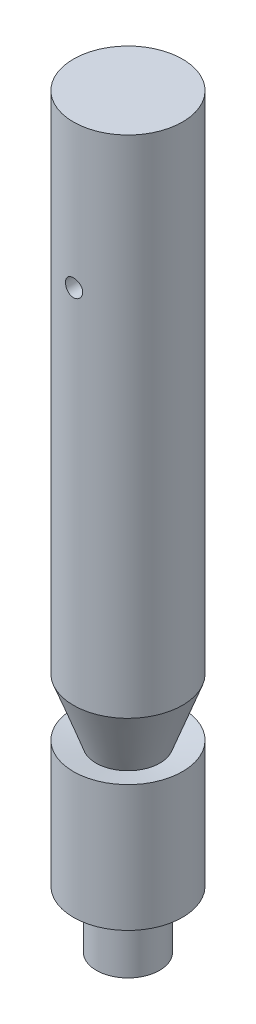
SolidWorks part; units mm, degrees
ref_plane "Alzado" through (0, 0, 0) normal (0, 0, 1) x (1, 0, 0)
ref_plane "Planta" through (0, 0, 0) normal (0, 1, 0) x (1, 0, 0)
ref_plane "Vista lateral" through (0, 0, 0) normal (1, 0, 0) x (0, 0, -1)
sketch "Croquis1" plane through (0, 0, 0) normal (0, 1, 0) x (1, 0, 0)
  circle A0 centre (0, 0) radius 9.5
  dimension "D1" = 19
extrude "Saliente-Extruir1" add sketch "Croquis1" along normal blind 120
sketch "Croquis2" plane through (0, 0, 0) normal (0, 0, 1) x (1, 0, 0)
  line L0 (-9.5, 22) -> (-9.5, 32)
  line L1 (-9.5, 120) -> (-9.5, 0) construction
  line L2 (-9.5, 32) -> (-5.5608, 21.3054)
  line L3 (-5.5608, 21.3054) -> (-9.5, 22)
  line L5 (-9.5, 0) -> (9.5, 0) construction
  dimension "D1" = 4
  dimension "D2" = 10
  dimension "D3" = 100
  dimension "D4" = 22
ref_axis "Eje1" through (0, 120, 0) along (0, -1, 0)
revolve "Cortar-Revolución1" cut sketch "Croquis2" angle 360 about axis through (0, 120, 0) along (0, -1, 0)
sketch "Croquis3" plane through (0, 0, 0) normal (0, -1, 0) x (1, 0, 0)
  circle A0 centre (0, 0) radius 5.5
  dimension "D1" = 11
extrude "Saliente-Extruir2" add sketch "Croquis3" along normal blind 10
sketch "Croquis4" plane through (0, -10, 0) normal (0, -1, 0) x (1, 0, 0)
  circle A0 centre (0, 0) radius 2.5
  dimension "D1" = 5
extrude "Cortar-Extruir1" cut sketch "Croquis4" against normal blind 110
sketch "Croquis5" plane through (0, 0, 0) normal (0, 0, 1) x (1, 0, 0)
  line L0 (0, 120) -> (0, 0) construction
  line L1 (9.5, 120) -> (-9.5, 120) construction
  circle A0 centre (0, 95) radius 1.5
  dimension "D1" = 3
  dimension "D2" = 25
extrude "Cortar-Extruir2" cut sketch "Croquis5" against normal blind 110 and the other way blind 110
